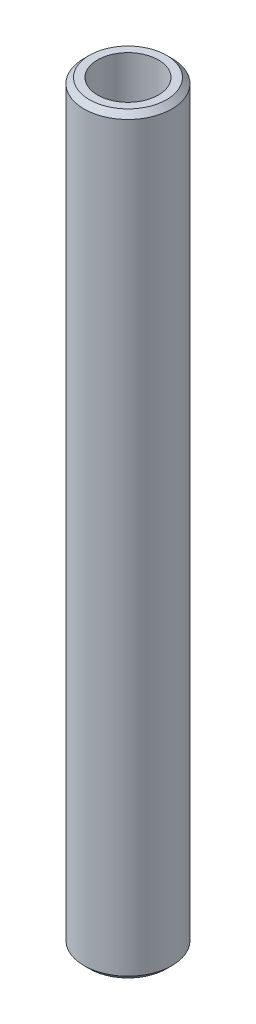
SolidWorks part; units mm, degrees
ref_plane "Front Plane" through (0, 0, 0) normal (0, 0, 1) x (1, 0, 0)
ref_plane "Top Plane" through (0, 0, 0) normal (0, 1, 0) x (1, 0, 0)
ref_plane "Right Plane" through (0, 0, 0) normal (1, 0, 0) x (0, 0, -1)
sketch "Sketch1" plane through (0, 0, 0) normal (0, 1, 0) x (1, 0, 0)
  circle A0 centre (0, 0) radius 35
  dimension "SHAFT_OD" = 70
extrude "Boss-Extrude1" add sketch "Sketch1" along normal blind 600
sketch "Sketch2" plane through (0, 0, 0) normal (0, 1, 0) x (1, 0, 0)
  circle A0 centre (0, 0) radius 24.2686
  dimension "BORE_D" = 48.5372
extrude "Cut-Extrude1" cut sketch "Sketch2" along normal through all
chamfer "Chamfer1" distance 4.2754 angle 45 2 edges at (0, 600, 35) (0, 0, 35)
